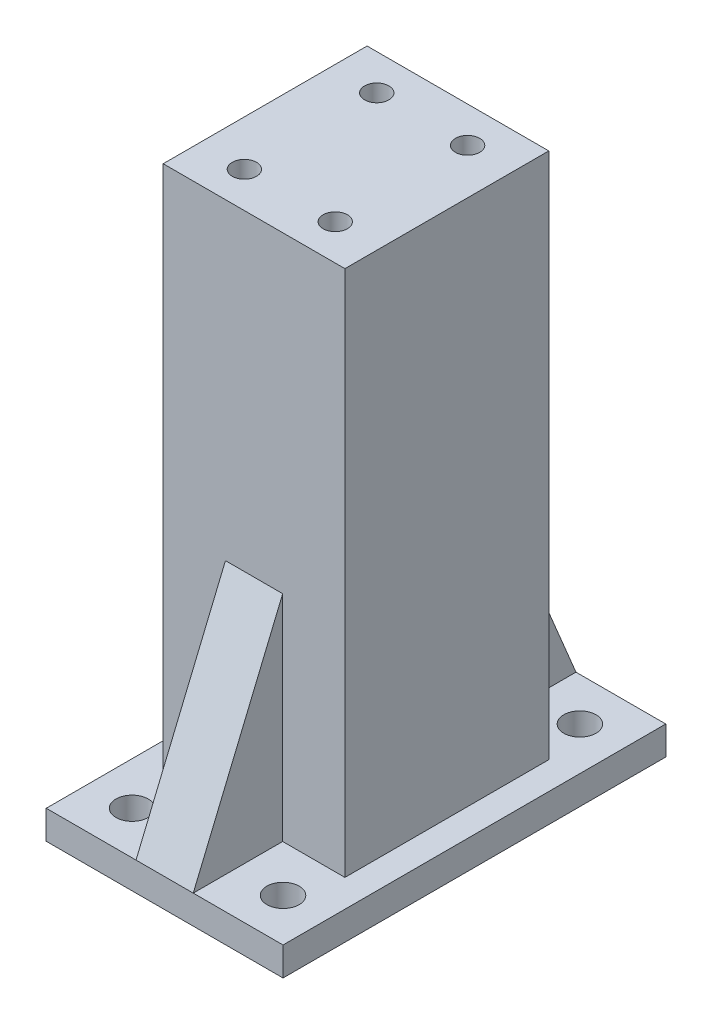
SolidWorks part; units mm, degrees
material "Custom Plastic"
ref_plane "Front Plane" through (0, 0, 0) normal (0, 0, 1) x (1, 0, 0)
ref_plane "Top Plane" through (0, 0, 0) normal (0, 1, 0) x (1, 0, 0)
ref_plane "Right Plane" through (0, 0, 0) normal (1, 0, 0) x (0, 0, -1)
sketch "Sketch10" plane through (0, 0, 0) normal (0, 1, 0) x (1, 0, 0)
  line L1 (16.55, -26.75) -> (-16.55, -26.75)
  line L2 (16.55, -26.75) -> (16.55, 26.75)
  line L3 (16.55, 26.75) -> (-16.55, 26.75)
  line L4 (-16.55, -26.75) -> (-16.55, 26.75)
  line L5 (16.55, -26.75) -> (-16.55, 26.75) construction
  line L6 (16.55, 26.75) -> (-16.55, -26.75) construction
  point P0 (0, 0)
  dimension "D1" = 53.5
  dimension "D2" = 33.1
extrude "Boss-Extrude7" add sketch "Sketch10" against normal blind 4
sketch "Sketch12" plane through (0, 0, 0) normal (0, 1, 0) x (1, 0, 0)
  line L0 (10.55, 20.75) -> (10.55, 26.75) construction
  line L1 (-10.55, -20.75) -> (10.55, -20.75) construction
  line L2 (-10.55, -20.75) -> (-10.55, 20.75) construction
  line L3 (-10.55, 20.75) -> (10.55, 20.75) construction
  line L4 (10.55, -20.75) -> (10.55, 20.75) construction
  line L5 (-10.55, -20.75) -> (10.55, 20.75) construction
  line L6 (-10.55, 20.75) -> (10.55, -20.75) construction
  line L7 (16.55, 26.75) -> (-16.55, 26.75) construction
  line L8 (10.55, 20.75) -> (16.55, 20.75) construction
  line L9 (16.55, -26.75) -> (16.55, 26.75) construction
  circle A0 centre (-10.55, 20.75) radius 2.25
  circle A1 centre (10.55, 20.75) radius 2.25
  circle A2 centre (10.55, -20.75) radius 2.25
  circle A3 centre (-10.55, -20.75) radius 2.25
  point P0 (0, 0)
  dimension "D2" = 4.5
  dimension "D1" = 6
extrude "Cut-Extrude2" cut sketch "Sketch12" against normal through all
sketch "Sketch11" plane through (0, 0, 0) normal (0, 1, 0) x (1, 0, 0)
  line L1 (-12.7, -14.25) -> (12.7, -14.25)
  line L2 (-12.7, -14.25) -> (-12.7, 14.25)
  line L3 (-12.7, 14.25) -> (12.7, 14.25)
  line L4 (12.7, -14.25) -> (12.7, 14.25)
  line L5 (-12.7, -14.25) -> (12.7, 14.25) construction
  line L6 (-12.7, 14.25) -> (12.7, -14.25) construction
  point P0 (0, 0)
  dimension "D1" = 28.5
  dimension "D2" = 25.4
extrude "Boss-Extrude8" add sketch "Sketch11" along normal up to surface (73.7 mm away)
sketch "Sketch13" plane through (0, 0, 0) normal (1, 0, 0) x (0, 0, -1)
  line L0 (26.75, 0) -> (14.25, 30)
  line L1 (26.75, 0) -> (-26.75, 0) construction
  line L2 (14.25, 73.7) -> (14.25, 0) construction
  dimension "D1" = 30
rib "Rib3" sketch "Sketch13" sketch "Sketch13" thickness 8 extrusion direction parallel to sketch draft on no parameters "D1"=8
mirror "Mirror1" about plane through (0, 0, 0) normal (0, 0, 1) of "Rib3"
sketch "Sketch14" plane through (0, 73.7, 0) normal (0, 1, 0) x (1, 0, 0)
  line L0 (12.7, 14.25) -> (4, 14.25) construction
  line L1 (-6.35, -9.25) -> (6.35, -9.25) construction
  line L2 (-6.35, -9.25) -> (-6.35, 9.25) construction
  line L3 (-6.35, 9.25) -> (6.35, 9.25) construction
  line L4 (6.35, -9.25) -> (6.35, 9.25) construction
  line L5 (-6.35, -9.25) -> (6.35, 9.25) construction
  line L6 (-6.35, 9.25) -> (6.35, -9.25) construction
  line L7 (-12.7, -14.25) -> (12.7, -14.25) construction
  line L8 (-2.9436, 9.25) -> (-4.6468, 12.2)
  line L9 (-4.6468, 12.2) -> (-8.0532, 12.2)
  line L10 (-8.0532, 12.2) -> (-9.7564, 9.25)
  line L11 (-9.7564, 9.25) -> (-8.0532, 6.3)
  line L12 (-8.0532, 6.3) -> (-4.6468, 6.3)
  line L13 (-4.6468, 6.3) -> (-2.9436, 9.25)
  line L14 (9.7564, 9.25) -> (8.0532, 12.2)
  line L15 (8.0532, 12.2) -> (4.6468, 12.2)
  line L16 (4.6468, 12.2) -> (2.9436, 9.25)
  line L17 (2.9436, 9.25) -> (4.6468, 6.3)
  line L18 (4.6468, 6.3) -> (8.0532, 6.3)
  line L19 (8.0532, 6.3) -> (9.7564, 9.25)
  line L20 (9.7564, -9.25) -> (8.0532, -6.3)
  line L21 (8.0532, -6.3) -> (4.6468, -6.3)
  line L22 (4.6468, -6.3) -> (2.9436, -9.25)
  line L23 (2.9436, -9.25) -> (4.6468, -12.2)
  line L24 (4.6468, -12.2) -> (8.0532, -12.2)
  line L25 (8.0532, -12.2) -> (9.7564, -9.25)
  line L26 (-2.9436, -9.25) -> (-4.6468, -6.3)
  line L27 (-4.6468, -6.3) -> (-8.0532, -6.3)
  line L28 (-8.0532, -6.3) -> (-9.7564, -9.25)
  line L29 (-9.7564, -9.25) -> (-8.0532, -12.2)
  line L30 (-8.0532, -12.2) -> (-4.6468, -12.2)
  line L31 (-4.6468, -12.2) -> (-2.9436, -9.25)
  circle A0 centre (-6.35, 9.25) radius 1.7
  circle A1 centre (6.35, 9.25) radius 1.7
  circle A2 centre (6.35, -9.25) radius 1.7
  circle A3 centre (-6.35, -9.25) radius 1.7
  circle A4 centre (-6.35, 9.25) radius 2.95 construction
  circle A5 centre (6.35, 9.25) radius 2.95 construction
  circle A6 centre (6.35, -9.25) radius 2.95 construction
  circle A7 centre (-6.35, -9.25) radius 2.95 construction
  point P1 (0, 0)
  dimension "D3" = 3.4
  dimension "D1" = 12.7
  dimension "D2" = 5
  dimension "D4" = 5.9
extrude "Cut-Extrude3" cut sketch "Sketch14" against normal blind 12 contours A0 | A1 | A3 | A2 region at (-6.35, 73.7, -9.25) region at (6.35, 73.7, -9.25) region at (6.35, 73.7, 9.25) region at (-6.35, 73.7, 9.25)
extrude "Cut-Extrude5" cut sketch "Sketch14<3>" against normal blind 2.5 from offset 5 offset against normal yes
sketch "Sketch14<3>" plane through (0, 73.7, 0) normal (0, 1, 0) x (1, 0, 0) same geometry as "Sketch14"
